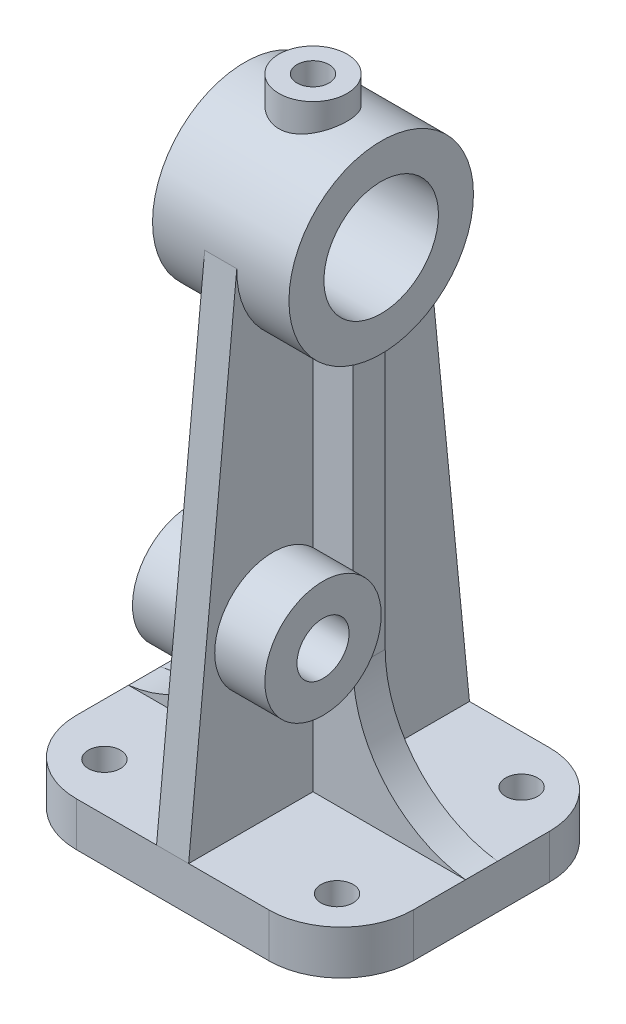
SolidWorks part; units mm, degrees
ref_plane "Front Plane" through (0, 0, 0) normal (0, 0, 1) x (1, 0, 0)
ref_plane "Top Plane" through (0, 0, 0) normal (0, 1, 0) x (1, 0, 0)
ref_plane "Right Plane" through (0, 0, 0) normal (1, 0, 0) x (0, 0, -1)
sketch "Sketch1" plane through (0, 0, 0) normal (0, 1, 0) x (1, 0, 0)
  line L1 (-24, -35) -> (24, -35)
  line L2 (-42, -17) -> (-42, 17)
  line L3 (-24, 35) -> (24, 35)
  line L4 (42, -17) -> (42, 17)
  line L5 (-42, -35) -> (42, 35) construction
  line L6 (-42, 35) -> (42, -35) construction
  arc A0 (-24, -35) -> (-42, -17) centre (-24, -17) cw
  arc A1 (-42, 17) -> (-24, 35) centre (-24, 17) cw
  arc A2 (42, 17) -> (24, 35) centre (24, 17) ccw
  arc A3 (42, -17) -> (24, -35) centre (24, -17) cw
  point P0 (0, 0)
  dimension "D3" = 18
  dimension "D1" = 70
  dimension "D2" = 84
extrude "Boss-Extrude1" add sketch "Sketch1" along normal blind 11
sketch "Sketch2" plane through (0, 0, 0) normal (1, 0, 0) x (0, 0, -1)
  line L0 (0, 0) -> (0, 133) construction
  line L1 (-17, 0) -> (17, 0) construction
  circle A0 centre (0, 133) radius 14.275
  circle A1 centre (0, 133) radius 23
  dimension "D1" = 46
  dimension "D2" = 28.55
  dimension "D3" = 133
extrude "Boss-Extrude2" add sketch "Sketch2" along normal mid plane 34 separate body
sketch "Sketch3" plane through (0, 0, 0) normal (1, 0, 0) x (0, 0, -1)
  line L0 (-35, 11) -> (-22.9963, 133.4129)
  line L1 (-22.9963, 133.4129) -> (22.9963, 133.4129) construction
  line L2 (22.9963, 133.4129) -> (35, 11)
  line L3 (35, 11) -> (-35, 11)
  circle A0 centre (0, 133) radius 23 construction
  arc A1 (-22.9963, 133.4129) -> (22.9963, 133.4129) centre (0, 133) ccw
  dimension "D1" = 123
extrude "Boss-Extrude3" add sketch "Sketch3" along normal mid plane 8
sketch "Sketch6" plane through (0, 11, 0) normal (0, 1, 0) x (1, 0, 0)
  line L0 (0, 0) -> (42, 0) construction
  line L1 (42, -17) -> (42, 17) construction
  line L2 (0, 0) -> (0, -35) construction
  line L3 (4, -35) -> (-4, -35) construction
  circle A1 centre (29, -23) radius 4
  circle A5 centre (29, 23) radius 4
  circle A6 centre (-29, -23) radius 4
  circle A7 centre (-29, 23) radius 4
  dimension "D1" = 23
  dimension "D3" = 8
  dimension "D2" = 29
extrude "Cut-Extrude1" cut sketch "Sketch6" against normal through all
ref_plane "Plane3" through (0, 162, 0) normal (0, -1, 0) x (-1, 0, 0)
sketch "Sketch9" plane through (0, 162, 0) normal (0, -1, 0) x (-1, 0, 0)
  circle A0 centre (0, 0) radius 8.5
  circle A1 centre (0, 0) radius 4
  dimension "D1" = 8
  dimension "D2" = 17
extrude "Boss-Extrude4" add sketch "Sketch9" along normal up to next
extrude "Cut-Extrude2" cut sketch "Sketch9<3>" along normal up to surface (15.2969 mm away) contours A1 region at (0, 162, 0) up to face at (17, 133, -14.275)
sketch "Sketch9<3>" plane through (0, 162, 0) normal (0, -1, 0) x (-1, 0, 0) same geometry as "Sketch9"
sketch "Sketch10" plane through (0, 0, 0) normal (0, 0, 1) x (1, 0, 0)
  line L0 (14, 113) -> (14, 42.749)
  line L1 (4, 133.4129) -> (4, 11) construction
  line L2 (4, 110) -> (17, 110) construction
  line L3 (14, 113) -> (4, 113)
  line L4 (4, 110) -> (4, 133.4129) construction
  line L5 (4, 113) -> (4, 11)
  line L6 (4, 11) -> (42, 11)
  arc A0 (42, 11) -> (14, 42.749) centre (46, 42.749) cw
  point P4 (9.5105, 110)
  dimension "D3" = 32
  dimension "D1" = 10
  dimension "D2" = 3
extrude "Boss-Extrude5" add sketch "Sketch10" along normal mid plane 8
mirror "Mirror1" about plane through (0, 0, 0) normal (1, 0, 0) of "Boss-Extrude5"
sketch "Sketch12" plane through (0, 0, 0) normal (1, 0, 0) x (0, 0, -1)
  circle A0 centre (0, 133) radius 81 construction
  circle A1 centre (-14, 53.219) radius 6.5
  circle A2 centre (-14, 53.219) radius 14.5
  dimension "D1" = 162
  dimension "D2" = 13
  dimension "D3" = 29
  dimension "D4" = 14
extrude "Boss-Extrude6" add sketch "Sketch12" along normal mid plane 33
extrude "Cut-Extrude3" cut sketch "Sketch12<2>" against normal through all and the other way through all contours A1
sketch "Sketch12<2>" plane through (0, 0, 0) normal (1, 0, 0) x (0, 0, -1) same geometry as "Sketch12"
